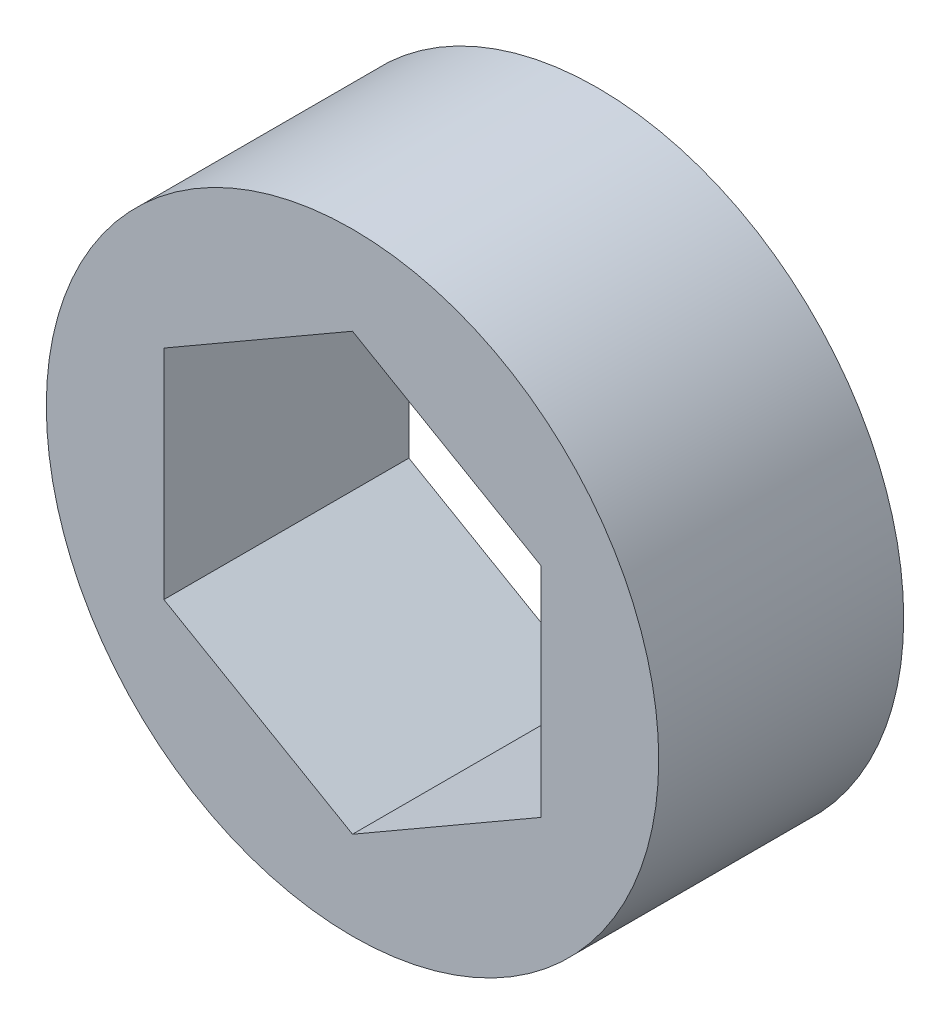
SolidWorks part; units mm, degrees
material "POM Acetal Copolymer"
ref_plane "Front" through (0, 0, 0) normal (0, 0, 1) x (1, 0, 0)
ref_plane "Top" through (0, 0, 0) normal (0, 1, 0) x (1, 0, 0)
ref_plane "Right" through (0, 0, 0) normal (1, 0, 0) x (0, 0, -1)
sketch "Sketch1" plane through (0, 0, 0) normal (0, 0, 1) x (1, 0, 0)
  line L1 (0, 5.6459) -> (-4.8895, 2.823)
  line L2 (-4.8895, 2.823) -> (-4.8895, -2.823)
  line L3 (-4.8895, -2.823) -> (0, -5.6459)
  line L4 (0, -5.6459) -> (4.8895, -2.823)
  line L5 (4.8895, -2.823) -> (4.8895, 2.823)
  line L6 (4.8895, 2.823) -> (0, 5.6459)
  circle A0 centre (0, 0) radius 7.9375
  circle A1 centre (0, 0) radius 4.8895 construction
  dimension "D2" = 15.875
  dimension "D1" = 9.779
extrude "Boss-Extrude1" add sketch "Sketch1" along normal blind 6.35
